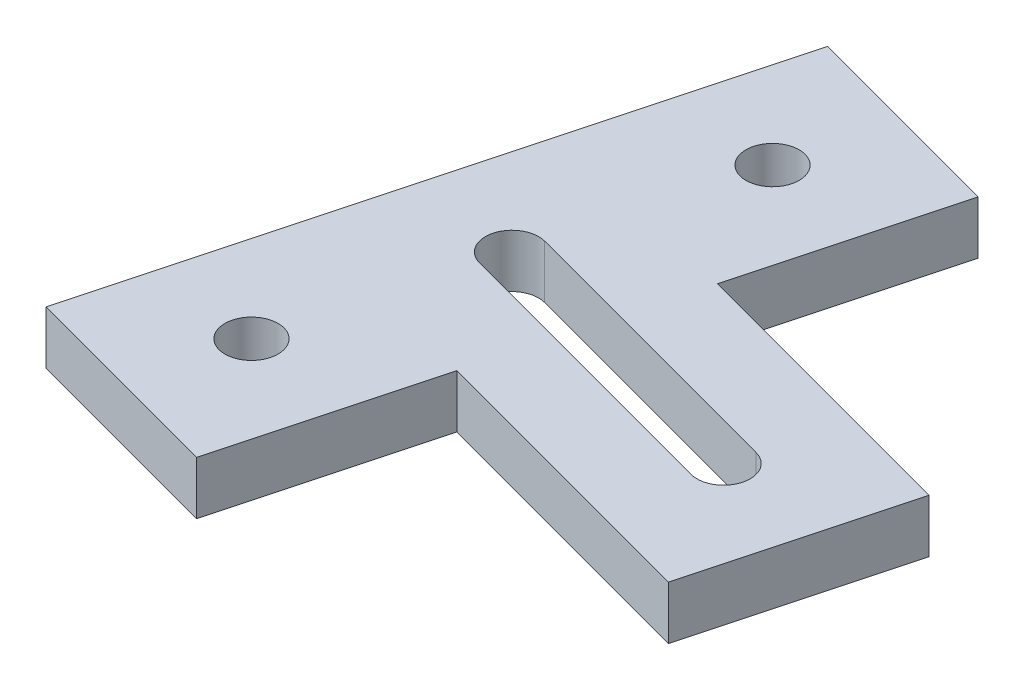
SolidWorks part; units mm, degrees
material "6061 Alloy"
ref_plane "Front Plane" through (0, 0, 0) normal (0, 0, 1) x (1, 0, 0)
ref_plane "Top Plane" through (0, 0, 0) normal (0, 1, 0) x (1, 0, 0)
ref_plane "Right Plane" through (0, 0, 0) normal (1, 0, 0) x (0, 0, -1)
sketch "Sketch1" plane through (0, 0, 0) normal (0, 1, 0) x (1, 0, 0)
  line L0 (0, 81.727) -> (0, -81.727) construction
  line L1 (-12.7, -81.727) -> (12.7, -81.727) construction
  line L2 (-12.7, -81.727) -> (-12.7, 81.727) construction
  line L3 (-12.7, 81.727) -> (12.7, 81.727) construction
  line L4 (12.7, -81.727) -> (12.7, 81.727) construction
  line L5 (-12.7, -81.727) -> (12.7, 81.727) construction
  line L6 (-12.7, 81.727) -> (12.7, -81.727) construction
  line L7 (0, 69.027) -> (-34.5135, -59.7792) construction
  line L8 (-34.5135, -59.7792) -> (0, -69.027) construction
  line L9 (-34.5135, -59.7792) -> (-41.0875, -84.3137) construction
  line L10 (-18.9593, -50.7989) -> (15.5543, -60.0468)
  line L11 (-12.3853, -26.2644) -> (-36.9198, -19.6904)
  line L12 (-12.3853, -26.2644) -> (-32.1073, -99.8679)
  line L13 (-32.1073, -99.8679) -> (-56.6418, -93.2939)
  line L14 (-36.9198, -19.6904) -> (-56.6418, -93.2939)
  line L15 (-12.3853, -26.2644) -> (-56.6418, -93.2939) construction
  line L16 (-32.1073, -99.8679) -> (-36.9198, -19.6904) construction
  line L17 (15.5543, -60.0468) -> (8.9803, -84.5813)
  line L18 (8.9803, -84.5813) -> (-25.5333, -75.3334)
  line L19 (-0.8218, -72.0939) -> (-35.3353, -62.846)
  line L20 (-33.6918, -56.7124) -> (0.8218, -65.9602)
  circle A0 centre (0, -69.027) radius 3.175
  circle A2 centre (0, 69.027) radius 3.175 construction
  circle A3 centre (-34.5135, -59.7792) radius 3.175
  circle A4 centre (-27.9395, -35.2447) radius 3.175
  circle A5 centre (-41.0875, -84.3137) radius 3.175
  circle A6 centre (0, -69.027) radius 12.7 construction
  point P0 (0, 0)
  point P31 (-14.9286, -24.5116)
  dimension "D3" = 15
  dimension "D1" = 6.35
  dimension "D8" = 25.4
  dimension "D11" = 25.4
  dimension "D2" = 25.4
  dimension "D4" = 133.35
  dimension "D5" = 138.0541
  dimension "D6" = 12.7
  dimension "D7" = 12.7
  dimension "D9" = 25.4
  dimension "D10" = 25.4
  dimension "D12" = 12.7
extrude "Boss-Extrude1" add sketch "Sketch1" along normal blind 6.35 contours A3 L20 L12 L11 L14 L13 L19 A5 A4 | A0 L19 L12 L18 L17 L10 L20 region at (-21.0765, 0, 55.1621) region at (-1.8402, 0, 55.9366)
fillet "Fillet2" radius 12.7 rebuild error yes
fillet "Fillet3" radius 2.1167 rebuild error yes
